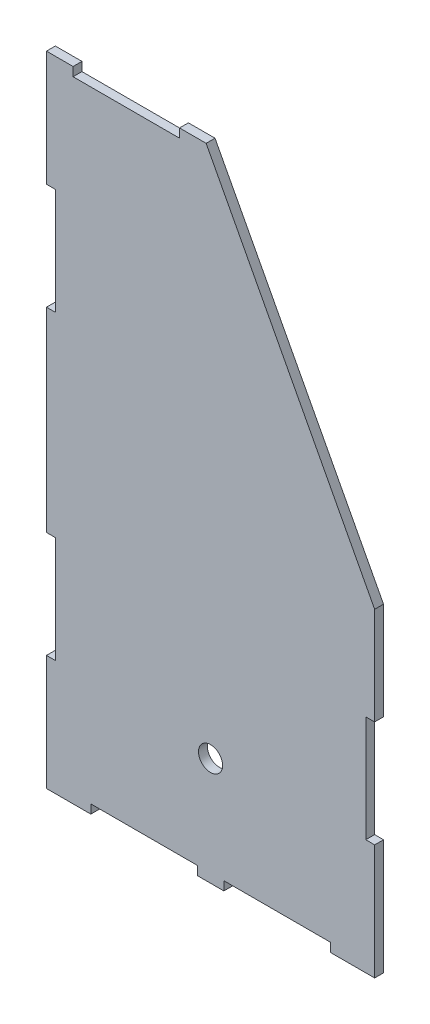
SolidWorks part; units mm, degrees
ref_plane "Front Plane" through (0, 0, 0) normal (0, 0, 1) x (1, 0, 0)
ref_plane "Top Plane" through (0, 0, 0) normal (0, 1, 0) x (1, 0, 0)
ref_plane "Right Plane" through (0, 0, 0) normal (1, 0, 0) x (0, 0, -1)
sketch "Sketch1" plane through (0, 0, 0) normal (0, 0, 1) x (1, 0, 0)
  line L0 (435.5199, 642.8699) -> (556.1699, 414.2699)
  line L1 (321.2199, 642.8699) -> (435.5199, 642.8699)
  line L2 (321.2199, 642.8699) -> (321.2199, 185.6699)
  line L3 (321.2199, 185.6699) -> (556.1699, 185.6699)
  line L4 (556.1699, 414.2699) -> (556.1699, 185.6699)
  dimension "D1" = 234.95
  dimension "D2" = 457.2
  dimension "D3" = 114.3
  dimension "D4" = 228.6
extrude "Boss-Extrude3" add sketch "Sketch1" along normal blind 6.35
sketch "Sketch2" plane through (0, 0, 6.35) normal (0, 0, 1) x (1, 0, 0)
  line L0 (327.5699, 642.8699) -> (327.5699, 185.6699) construction
  line L1 (435.5199, 642.8699) -> (321.2199, 642.8699) construction
  line L2 (321.2199, 185.6699) -> (556.1699, 185.6699) construction
  line L3 (321.2199, 192.0199) -> (556.1699, 192.0199) construction
  line L4 (321.2199, 642.8699) -> (321.2199, 185.6699) construction
  line L5 (556.1699, 185.6699) -> (556.1699, 414.2699) construction
  line L6 (321.2199, 636.5199) -> (438.8713, 636.5199) construction
  line L7 (549.8199, 185.6699) -> (549.8199, 426.3014) construction
  line L8 (556.1699, 414.2699) -> (435.5199, 642.8699) construction
  line L10 (416.4699, 642.8699) -> (340.2699, 642.8699)
  line L11 (416.4699, 642.8699) -> (416.4699, 636.5199)
  line L12 (416.4699, 636.5199) -> (340.2699, 636.5199)
  line L13 (340.2699, 642.8699) -> (340.2699, 636.5199)
  line L14 (321.2199, 560.3199) -> (327.5699, 560.3199)
  line L15 (321.2199, 560.3199) -> (321.2199, 484.1199)
  line L16 (321.2199, 484.1199) -> (327.5699, 484.1199)
  line L17 (327.5699, 560.3199) -> (327.5699, 484.1199)
  line L18 (321.2199, 344.4199) -> (327.5699, 344.4199)
  line L19 (321.2199, 344.4199) -> (321.2199, 268.2199)
  line L20 (321.2199, 268.2199) -> (327.5699, 268.2199)
  line L21 (327.5699, 344.4199) -> (327.5699, 268.2199)
  line L22 (352.9699, 192.0199) -> (429.1699, 192.0199)
  line L23 (352.9699, 192.0199) -> (352.9699, 185.6699)
  line L24 (352.9699, 185.6699) -> (429.1699, 185.6699)
  line L25 (429.1699, 192.0199) -> (429.1699, 185.6699)
  line L26 (448.2199, 192.0199) -> (524.4199, 192.0199)
  line L27 (448.2199, 192.0199) -> (448.2199, 185.6699)
  line L28 (448.2199, 185.6699) -> (524.4199, 185.6699)
  line L29 (524.4199, 192.0199) -> (524.4199, 185.6699)
  line L30 (549.8199, 344.4199) -> (556.1699, 344.4199)
  line L31 (549.8199, 344.4199) -> (549.8199, 268.2199)
  line L32 (549.8199, 268.2199) -> (556.1699, 268.2199)
  line L33 (556.1699, 344.4199) -> (556.1699, 268.2199)
  point P38 (552.9949, 268.2199)
  dimension "D1" = 6.35
  dimension "D2" = 6.35
  dimension "D3" = 6.35
  dimension "D4" = 6.35
  dimension "D6" = 76.2
  dimension "D8" = 82.55
  dimension "D9" = 82.55
  dimension "D5" = 19.05
  dimension "D10" = 76.2
  dimension "D11" = 76.2
  dimension "D12" = 19.05
  dimension "D14" = 82.55
  dimension "D7" = 76.2
  dimension "D13" = 31.75
extrude "Cut-Extrude1" cut sketch "Sketch2" against normal through all
sketch "Sketch3" plane through (0, 0, 0) normal (0, 0, 1) x (1, 0, 0)
  line L0 (429.1699, 185.6699) -> (448.2199, 185.6699) construction
  line L1 (556.1699, 185.6699) -> (556.1699, 268.2199) construction
  circle A0 centre (438.6949, 262.9891) radius 8.636
  dimension "D3" = 17.272
  dimension "D1" = 77.3192
  dimension "D2" = 117.475
extrude "Cut-Extrude3" cut sketch "Sketch3" against normal through all and the other way through all
equation "\"width\"= 9in"
equation "\"Height\"= 18in"
equation "\"D3@Sketch1\"=\"width\"/2"
equation "\"D4@Sketch1\"=\"Height\"/2"
equation "\"thick\"= 0.25"
equation "\"D1@Sketch2\"=\"thick\""
equation "\"D2@Sketch2\"=\"thick\""
equation "\"D3@Sketch2\"=\"thick\""
equation "\"D4@Sketch2\"=\"thick\""
equation "\"D2@Sketch1\"=\"Height\""
equation "\"D1@Sketch1\"= \"width\" + \"thick\""
equation "\"D1@Boss-Extrude3\"=\"thick\""
